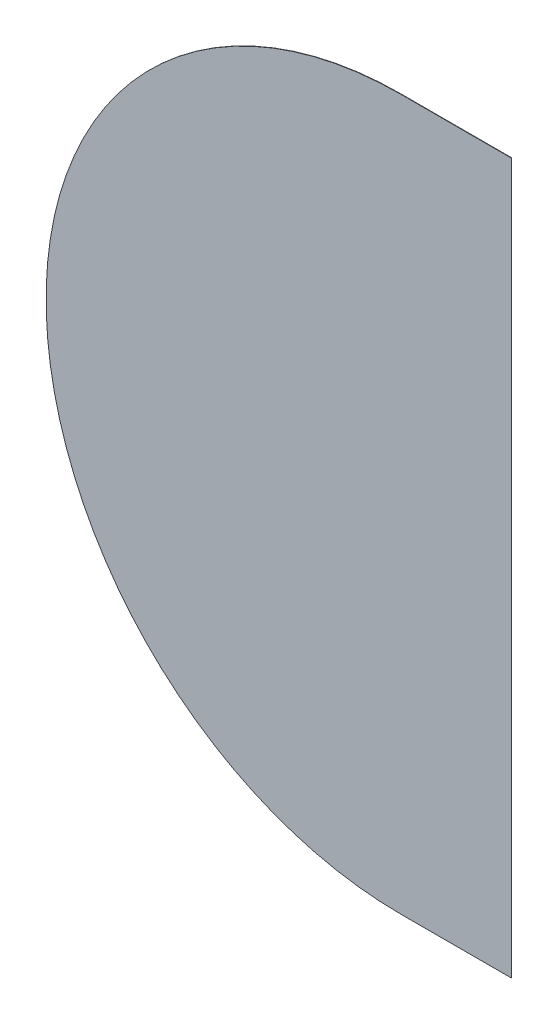
SolidWorks part; units mm, degrees
ref_plane "Front Plane" through (0, 0, 0) normal (0, 0, 1) x (1, 0, 0)
ref_plane "Top Plane" through (0, 0, 0) normal (0, 1, 0) x (1, 0, 0)
ref_plane "Right Plane" through (0, 0, 0) normal (1, 0, 0) x (0, 0, -1)
sketch "Sketch1" plane through (0, 0, 0) normal (0, 0, 1) x (1, 0, 0)
  line L1 (0, 0) -> (270, 0)
  line L2 (0, 0) -> (0, 1740) construction
  line L3 (0, 1740) -> (270, 1740)
  line L4 (270, 0) -> (270, 1740)
  arc A0 (0, 1740) -> (0, 0) centre (0, 870) ccw
  dimension "D1" = 270
  dimension "D2" = 1740
extrude "Boss-Extrude1" add sketch "Sketch1" along normal blind 1
